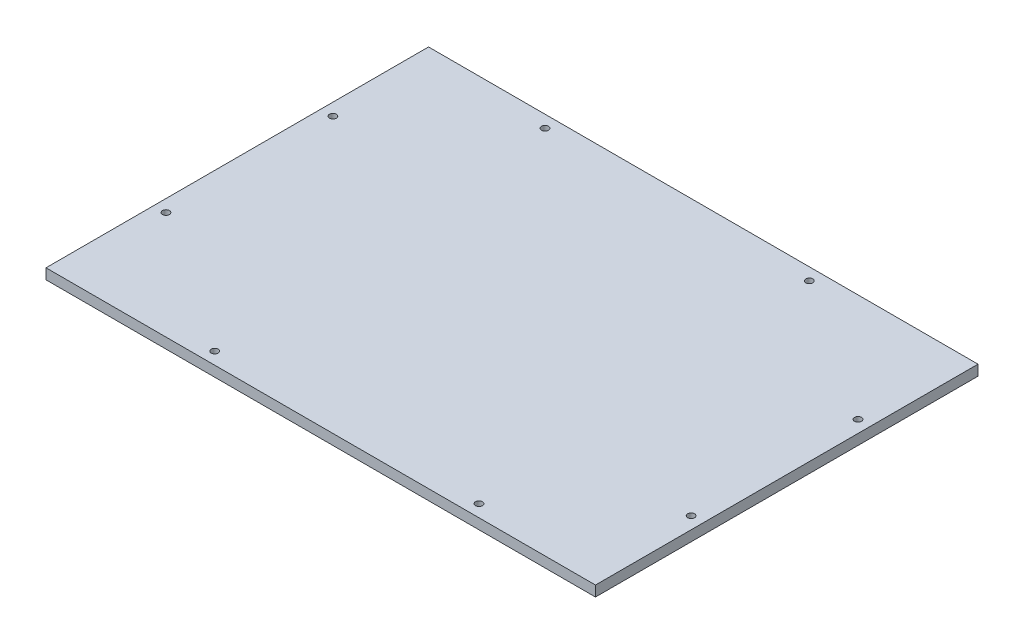
SolidWorks part; units mm, degrees
ref_plane "Front Plane" through (0, 0, 0) normal (0, 0, 1) x (1, 0, 0)
ref_plane "Top Plane" through (0, 0, 0) normal (0, 1, 0) x (1, 0, 0)
ref_plane "Right Plane" through (0, 0, 0) normal (1, 0, 0) x (0, 0, -1)
sketch "Sketch1" plane through (0, 0, 0) normal (0, 1, 0) x (1, 0, 0)
  line L1 (8.4883, 0) -> (510.1383, 0)
  line L2 (8.4883, 0) -> (8.4883, -349.25)
  line L3 (8.4883, -349.25) -> (510.1383, -349.25)
  line L4 (510.1383, 0) -> (510.1383, -349.25)
  dimension "D1" = 501.65
  dimension "D2" = 349.25
extrude "Boss-Extrude1" add sketch "Sketch1" along normal blind 9.525
sketch "Sketch2" plane through (0, 9.525, 0) normal (0, 1, 0) x (1, 0, 0)
  circle A0 centre (392.6633, -338.1375) radius 3.175
  circle A1 centre (151.3633, -338.1375) radius 3.175
  circle A2 centre (367.2633, -11.1125) radius 3.175
  circle A3 centre (125.9633, -11.1125) radius 3.175
  circle A4 centre (19.6008, -250.825) radius 3.175
  circle A5 centre (19.6008, -98.425) radius 3.175
  circle A6 centre (499.0258, -250.825) radius 3.175
  circle A7 centre (499.0258, -98.425) radius 3.175
extrude "Cut-Extrude1" cut sketch "Sketch2" against normal up to surface (9.525 mm away) up to face at (259.3133, 0, 174.625)
sketch "Sketch3" plane through (0, 9.525, 0) normal (0, 1, 0) x (1, 0, 0)
  line L0 (472.0383, -349.25) -> (472.0383, 3.175) construction
  line L1 (510.1383, -349.25) -> (8.4883, -349.25) construction
  line L2 (513.3133, 3.175) -> (5.3133, 3.175) construction
  line L3 (510.1383, 0) -> (510.1383, -349.25) construction
  line L4 (46.5883, -349.25) -> (46.5883, 0) construction
  line L5 (8.4883, 0) -> (510.1383, 0) construction
  line L6 (8.4883, -349.25) -> (8.4883, 0) construction
  line L7 (510.1383, -311.15) -> (8.4883, -311.15) construction
  line L8 (510.1383, -38.1) -> (8.4883, -38.1) construction
  point P18 (472.0383, -311.15)
  point P19 (472.0383, -38.1)
  point P20 (46.5883, -38.1)
  point P21 (46.5883, -311.15)
  dimension "D1" = 38.1
  dimension "D2" = 38.1
  dimension "D3" = 38.1
  dimension "D4" = 38.1
